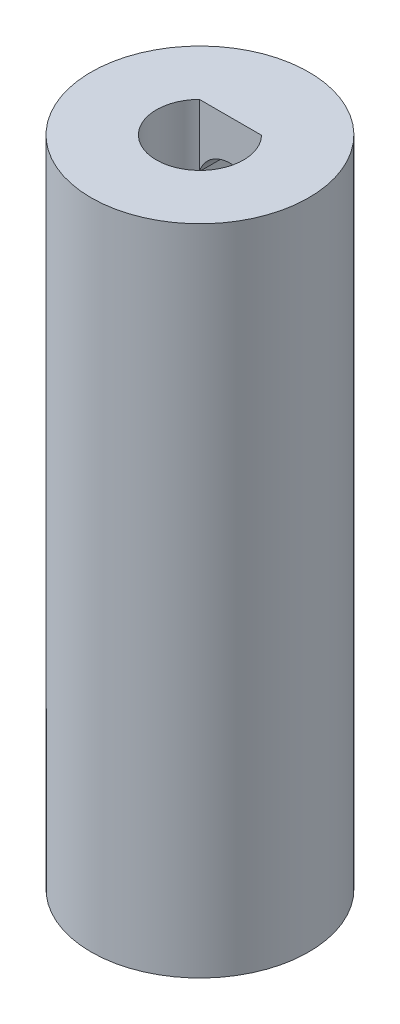
SolidWorks part; units mm, degrees
ref_plane "前视基准面" through (0, 0, 0) normal (0, 0, 1) x (1, 0, 0)
ref_plane "上视基准面" through (0, 0, 0) normal (0, 1, 0) x (1, 0, 0)
ref_plane "右视基准面" through (0, 0, 0) normal (1, 0, 0) x (0, 0, -1)
other "Configuration Table"
sketch "草图2" plane through (0, 0, 0) normal (0, 1, 0) x (1, 0, 0)
  circle A0 centre (0, 0) radius 5
  dimension "D1" = 10
extrude "凸台-拉伸2" add sketch "草图2" along normal blind 30
sketch "草图4" plane through (0, 30, 0) normal (0, 1, 0) x (1, 0, 0)
  line L0 (0, 0) -> (0, 1.4)
  line L1 (-1000, 1.4) -> (49000, 1.4)
  circle A0 centre (0, 0) radius 2
  dimension "D1" = 4
  dimension "D2" = 1.4
extrude "切除-拉伸1" cut sketch "草图4" against normal through all contours L1 A0 region at (0, 30, 0.1706)
sketch "草图5" plane through (0, 0, -1.4) normal (0, 0, 1) x (1, 0, 0)
  line L0 (0, 30) -> (0, 26.6692)
  line L1 (2, 30) -> (-2, 30) construction
  circle A0 centre (0, 26.6692) radius 1.5
  line M2 (-1.4283, 30) -> (-1.4283, 0)
  line M4 (1.4283, 0) -> (1.4283, 30)
  dimension "D1" = 3
extrude "切除-拉伸2" cut sketch "草图5" against normal up to next contours A0 M4 M2 region at (1.3869, 26.6692, -1.4)
